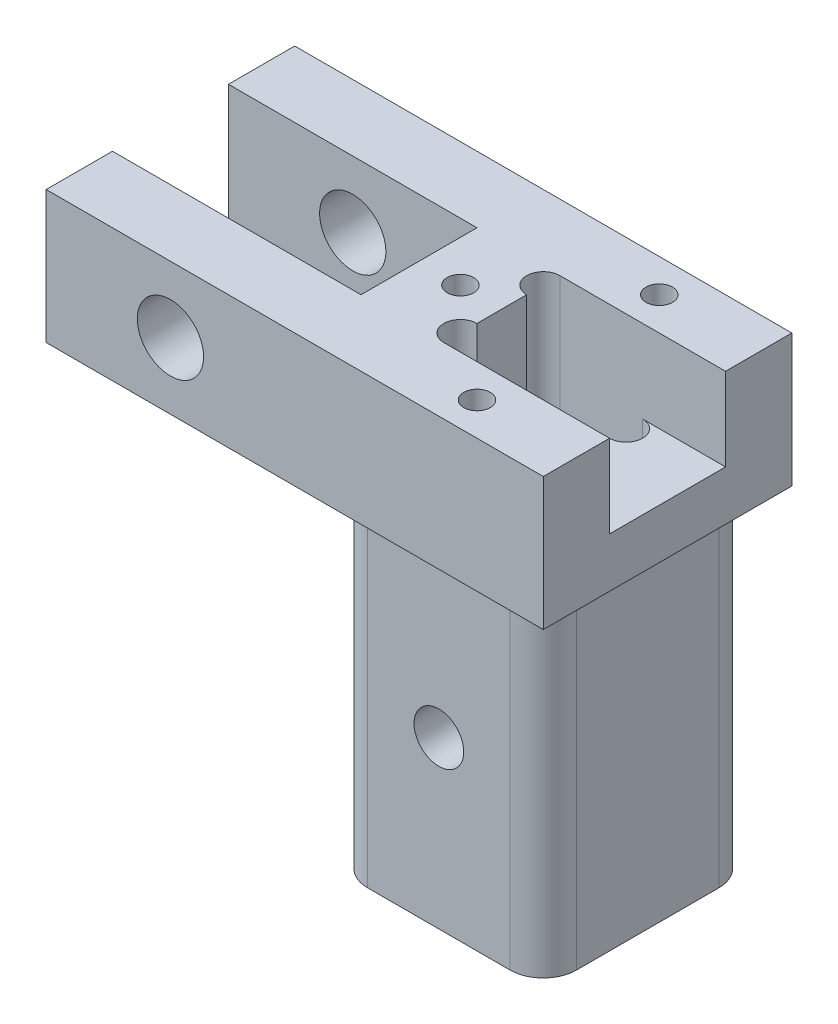
SolidWorks part; units mm, degrees
material "6061 合金"
ref_plane "前视基准面" through (0, 0, 0) normal (0, 0, 1) x (1, 0, 0)
ref_plane "上视基准面" through (0, 0, 0) normal (0, 1, 0) x (1, 0, 0)
ref_plane "右视基准面" through (0, 0, 0) normal (1, 0, 0) x (0, 0, -1)
sketch "草图1" plane through (0, 0, 0) normal (0, 1, 0) x (1, 0, 0)
  line L1 (-6.3, -6.3) -> (6.3, -6.3)
  line L2 (-6.3, -6.3) -> (-6.3, 6.3)
  line L3 (-6.3, 6.3) -> (6.3, 6.3)
  line L4 (6.3, -6.3) -> (6.3, 6.3)
  line L5 (-6.3, -6.3) -> (6.3, 6.3) construction
  line L6 (-6.3, 6.3) -> (6.3, -6.3) construction
  point P0 (0, 0)
  dimension "D1" = 12.6
  dimension "D2" = 12.6
extrude "凸台-拉伸1" add sketch "草图1" along normal blind 20
sketch "草图2" plane through (0, 20, 0) normal (0, 1, 0) x (1, 0, 0)
  line L1 (-7.5, -7.5) -> (7.5, -7.5)
  line L2 (-7.5, -7.5) -> (-7.5, 7.5)
  line L3 (-7.5, 7.5) -> (7.5, 7.5)
  line L4 (7.5, -7.5) -> (7.5, 7.5)
  line L5 (-7.5, -7.5) -> (7.5, 7.5) construction
  line L6 (-7.5, 7.5) -> (7.5, -7.5) construction
  point P0 (0, 0)
  dimension "D1" = 15
  dimension "D2" = 15
extrude "凸台-拉伸2" add sketch "草图2" along normal blind 3
sketch "草图3" plane through (0, 0, 6.3) normal (0, 0, 1) x (1, 0, 0)
  line L0 (0, 20) -> (0, 10) construction
  line L1 (-7.5, 20) -> (7.5, 20) construction
  circle A0 centre (0, 10) radius 1.5
  dimension "D2" = 3
  dimension "D1" = 10
extrude "切除-拉伸1" cut sketch "草图3" against normal through all
sketch "草图4" plane through (0, 0, 0) normal (0, -1, 0) x (1, 0, 0)
  circle A0 centre (0, 0) radius 2.6
  dimension "D1" = 5.2
extrude "切除-拉伸2" cut sketch "草图4" against normal blind 5
sketch "草图5" plane through (0, 0, -7.5) normal (0, 0, -1) x (-1, 0, 0)
  line L0 (7.5, 20) -> (22.5, 20)
  line L1 (22.5, 20) -> (22.5, 28)
  line L2 (22.5, 28) -> (7.5, 28)
  line L5 (-7.5, 23) -> (-7.5, 20)
  line L6 (-7.5, 20) -> (7.5, 20)
  line L7 (7.5, 28) -> (-7.5, 28)
  line L8 (-7.5, 28) -> (-7.5, 23)
  dimension "D1" = 15
  dimension "D2" = 8
extrude "凸台-拉伸3" add sketch "草图5" against normal blind 4
mirror "镜向1" about plane through (0, 0, 0) normal (0, 0, 1) of "凸台-拉伸3"
sketch "草图6" plane through (0, 0, 3.5) normal (0, 0, -1) x (-1, 0, 0)
  line L0 (22.5, 24) -> (30, 24) construction
  line L1 (22.5, 20) -> (22.5, 28) construction
  circle A0 centre (30, 24) radius 2
  dimension "D2" = 4
  dimension "D1" = 7.5
sketch "草图10" plane through (0, 0, -7.5) normal (0, 0, -1) x (-1, 0, 0)
  line L0 (22.5, 24) -> (15, 24) construction
  line L1 (22.5, 20) -> (22.5, 28) construction
  circle A0 centre (15, 24) radius 2
  dimension "D2" = 4
  dimension "D1" = 7.5
extrude "切除-拉伸5" cut sketch "草图10" against normal through all
sketch "草图11" plane through (0, 23, 0) normal (0, 1, 0) x (1, 0, 0)
  line L0 (7.5, 0) -> (0, 0) construction
  line L2 (7.5, -3.5) -> (7.5, 3.5) construction
  line L4 (2.5, 3.5) -> (-2.5, 3.5)
  line L5 (2.5, 3.5) -> (2.5, -3.5)
  line L6 (2.5, -3.5) -> (-2.5, -3.5)
  line L7 (-2.5, 3.5) -> (-2.5, -3.5)
  line L8 (2.5, 3.5) -> (-2.5, -3.5) construction
  line L9 (2.5, -3.5) -> (-2.5, 3.5) construction
  dimension "D1" = 7.5
  dimension "D2" = 7
  dimension "D3" = 5
extrude "切除-拉伸6" cut sketch "草图11" against normal blind 8
sketch "草图12" plane through (0, 23, 0) normal (0, 1, 0) x (1, 0, 0)
  line L0 (2.5, -3.5) -> (2.5, 3.5) construction
  line L1 (-2.5, 3.5) -> (-2.5, -3.5) construction
  line L2 (2.5, 3.5) -> (7.5, 3.5) construction
  line L3 (-7.5, 3.5) -> (-2.5, 3.5) construction
  line L4 (7.5, -3.5) -> (2.5, -3.5) construction
  line L5 (-2.5, -3.5) -> (-7.5, -3.5) construction
  circle A0 centre (2.5, -2.5) radius 1
  circle A1 centre (-2.5, -2.5) radius 1
  circle A2 centre (2.5, 2.5) radius 1
  circle A3 centre (-2.5, 2.5) radius 1
  dimension "D1" = 2
  dimension "D2" = 2
  dimension "D3" = 2
  dimension "D4" = 2
extrude "切除-拉伸7" cut sketch "草图12" against normal up to surface (8 mm away) up to face at (0, 15, 0)
fillet "圆角1" radius 2 4 edges at (-6.3, 10, 6.3) (-6.3, 10, -6.3) (6.3, 10, -6.3) (6.3, 10, 6.3)
sketch "草图13" plane through (0, 23, 0) normal (0, 1, 0) x (1, 0, 0)
  line L0 (-7.5, 3.5) -> (-7.5, -3.5)
  line L1 (-2.5, -3.5) -> (-7.5, -3.5) construction
  line L2 (-7.5, 3.5) -> (-7.5, -3.5) construction
  line L3 (-7.5, -3.5) -> (-2.5, -3.5)
  line L4 (-7.5, 3.5) -> (-2.5, 3.5)
  line L5 (-2.5, 1.5) -> (-2.5, -1.5)
  arc A0 (-2.5, -3.5) -> (-2.5, -1.5) centre (-2.5, -2.5) cw
  arc A2 (-2.5, -1.5) -> (-2.5, -3.5) centre (-2.5, -2.5) ccw construction
  arc A3 (-2.5, 3.5) -> (-2.5, 1.5) centre (-2.5, 2.5) ccw
extrude "凸台-拉伸4" add sketch "草图13" along normal up to surface (5 mm away) up to face at (-7.5, 28, -5.5)
sketch "草图14" plane through (0, 28, 0) normal (0, 1, 0) x (1, 0, 0)
  line L0 (7.5, 5.5) -> (1.5, 5.5) construction
  line L1 (7.5, 3.5) -> (7.5, 7.5) construction
  line L2 (-7.5, 0) -> (-2.5, 0) construction
  line L3 (-7.5, 3.5) -> (-7.5, -3.5) construction
  line L4 (-2.5, -1.5) -> (-2.5, 1.5) construction
  line L5 (7.5, -5.5) -> (1.5, -5.5) construction
  line L7 (7.5, -3.5) -> (7.5, -7.5) construction
  circle A0 centre (1.5, 5.5) radius 1.5
  circle A1 centre (-5, 0) radius 1.5
  circle A2 centre (1.5, -5.5) radius 1.5
  dimension "D3" = 3
  dimension "D4" = 3
  dimension "D5" = 3
  dimension "D1" = 6
  dimension "D2" = 6
hole_wizard "M2 螺纹孔1" positions "3D草图1" profile "草图15" tap size "M2" standard "GB"
sketch3d "3D草图1"
  point P0 (1.5, 28, -5.5)
  point P3 (-5, 28, 0)
  point P6 (1.5, 28, 5.5)
sketch "草图15" plane through (1.5, 28, -5.5) normal (1, 0, 0) x (0, 0, 1)
  line L0 (0, 0) -> (0, 6.4807)
  line L1 (0, 6.4807) -> (0.8, 6)
  line L2 (0.8, 6) -> (0.8, 0)
  line L5 (0.8, 0) -> (0, 0)
  line L10 (0, 6.4807) -> (-0.8, 6) construction
  line L11 (0, -6.35) -> (0, 107.95) construction
  dimension "螺纹孔钻头直径" = 1.6
  dimension "螺纹孔钻头深度" = 6
  dimension "导头角度" = 118
cosmetic thread "孔螺蚊线1" parameters "D1"=4, "D2"=2
cosmetic thread "孔螺蚊线2" parameters "D1"=4, "D2"=2
cosmetic thread "孔螺蚊线3" parameters "D1"=4, "D2"=2
